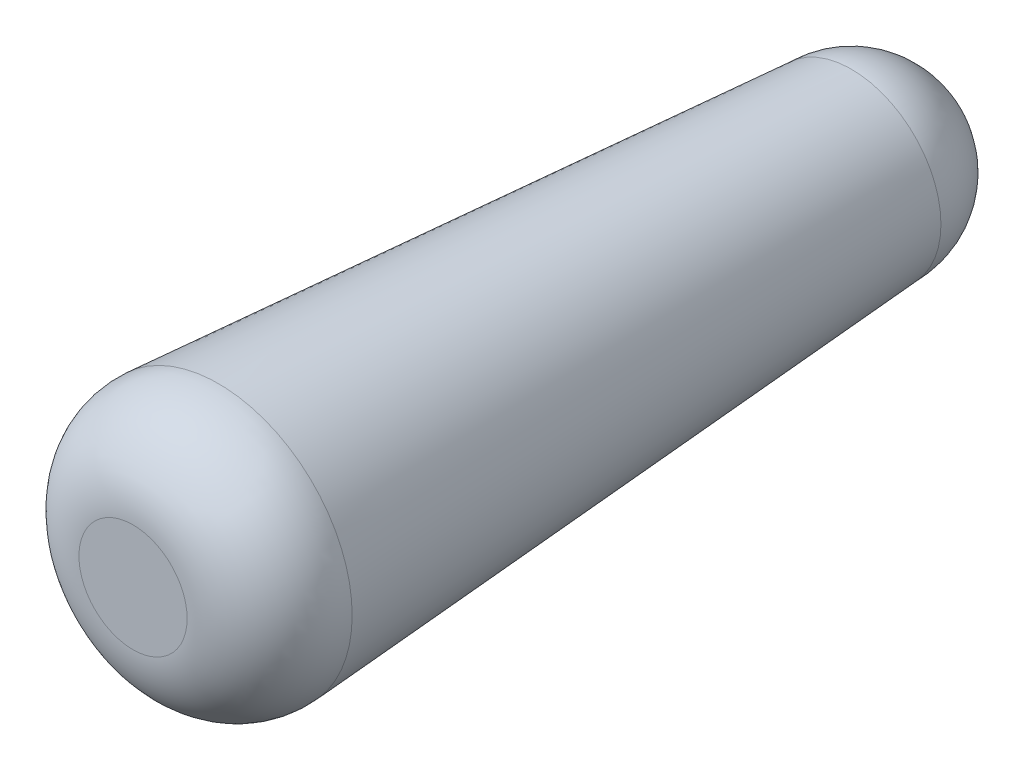
SolidWorks part; units mm, degrees
ref_plane "Front Plane" through (0, 0, 0) normal (0, 0, 1) x (1, 0, 0)
ref_plane "Top Plane" through (0, 0, 0) normal (0, 1, 0) x (1, 0, 0)
ref_plane "Right Plane" through (0, 0, 0) normal (1, 0, 0) x (0, 0, -1)
sketch "Sketch3" plane through (0, 0, 0) normal (0, 0, 1) x (1, 0, 0)
  circle A0 centre (0, 0) radius 88.9
  dimension "D1" = 177.8
extrude "Boss-Extrude1" add sketch "Sketch3" against normal blind 457.2 draft 4
sketch "Sketch4" plane through (0, 0, -457.2) normal (0, 0, -1) x (-1, 0, 0)
  point P0 (0, 0)
sketch "Sketch5" plane through (0, 0, 0) normal (0, 0, 1) x (1, 0, 0)
  point P0 (0, 0)
sketch "Sketch6" plane through (0, 0, 0) normal (1, 0, 0) x (0, 0, -1)
  line L0 (457.2, -56.9295) -> (457.2, 56.9295) construction
  line L1 (457.2, -56.9295) -> (457.2, 56.9295)
  arc A0 (457.2, -56.9295) -> (457.2, 56.9295) centre (457.2, 0) ccw
revolve "Revolve1" add sketch "Sketch6" angle 360 about L1
fillet "Fillet1" radius 50.8 1 edges at (88.9, 0, 0)
sketch3d "3DSketch1"
  line L0 (0, 0, 0) -> (0, 0, -457.2)
